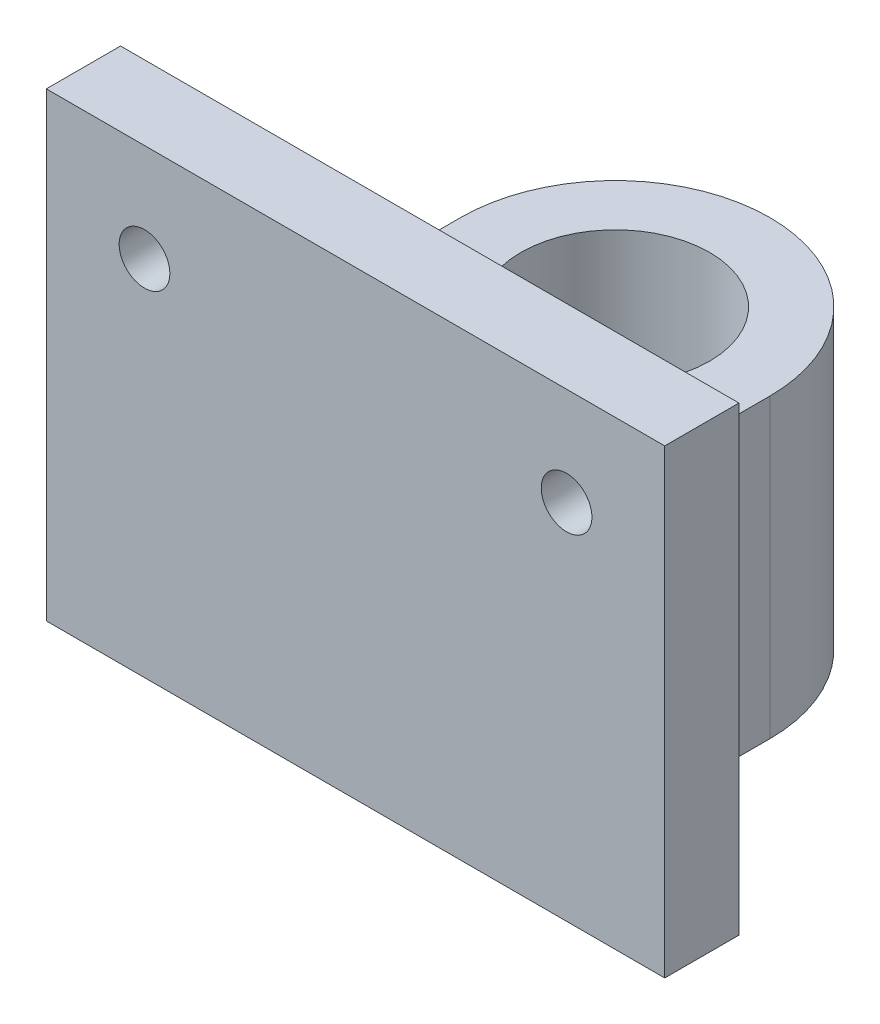
SolidWorks part; units mm, degrees
ref_plane "Front Plane" through (0, 0, 0) normal (0, 0, 1) x (1, 0, 0)
ref_plane "Top Plane" through (0, 0, 0) normal (0, 1, 0) x (1, 0, 0)
ref_plane "Right Plane" through (0, 0, 0) normal (1, 0, 0) x (0, 0, -1)
sketch "Profile-Sketch1" plane through (0, 0, 0) normal (0, 1, 0) x (1, 0, 0)
  line L0 (-25, -21) -> (25, -21)
  line L1 (25, -21) -> (25, -15)
  line L2 (-25, -21) -> (-25, -15)
  line L3 (-25, -15) -> (-22.5, -15)
  line L4 (-12.5, -5) -> (-12.5, 0)
  line L5 (25, -15) -> (22.5, -15)
  line L6 (12.5, -5) -> (12.5, 0)
  circle A0 centre (0, 0) radius 7.625
  arc A6 (12.5, 0) -> (-12.5, 0) centre (0, 0) ccw
  arc A7 (22.5, -15) -> (12.5, -5) centre (22.5, -5) cw
  arc A8 (-12.5, -5) -> (-22.5, -15) centre (-22.5, -5) cw
  dimension "D1" = 15.25
  dimension "D2" = 12.5
  dimension "D7" = 10
  dimension "D3" = 50
  dimension "D4" = 25
  dimension "D5" = 21
  dimension "D6" = 6
extrude "Profile-Boss-Extrude2" add sketch "Profile-Sketch1" along normal blind 37.2599
sketch "FasteningHoleSketch3" plane through (0, 0, 21) normal (0, 0, 1) x (1, 0, 0)
  line L0 (25, 37.2599) -> (25, 0) construction
  line L1 (-25, 37.2599) -> (-25, 0) construction
  line L2 (-25, 0) -> (25, 0) construction
  circle A2 centre (-17.0625, 29.3224) radius 2.05
  circle A3 centre (17.0625, 29.3224) radius 2.05
  dimension "D3" = 4.1
  dimension "D6" = 7.9375
  dimension "D2" = 29.3224
  dimension "D1" = 7.9375
extrude "FasteningHoleCut-Extrude8" cut sketch "FasteningHoleSketch3" against normal through all
sketch "LM8UUPlugSketch1" plane through (0, 0, 0) normal (0, -1, 0) x (1, 0, 0)
  circle A0 centre (0, 0) radius 7.625
  circle A1 centre (0, 0) radius 7.625 construction
  circle A2 centre (0, 0) radius 4.5
  dimension "D1" = 9
extrude "LM8UU plugBoss-Extrude1" add sketch "LM8UUPlugSketch1" along normal blind 0.0001 and the other way blind 1
sketch "Sketch2" plane through (0, 37.2599, 0) normal (0, 1, 0) x (1, 0, 0)
  line L0 (-12.5, 0) -> (-12.5, -5)
  line L1 (12.5, 0) -> (12.5, -5)
  line L2 (-22.5, -15) -> (22.5, -15)
  arc A0 (12.5, 0) -> (-12.5, 0) centre (0, 0) ccw
  arc A1 (12.5, 0) -> (-12.5, 0) centre (0, 0) ccw construction
  arc A2 (-22.5, -15) -> (-12.5, -5) centre (-22.5, -5) ccw
  arc A3 (-22.5, -15) -> (-12.5, -5) centre (-22.5, -5) ccw construction
  arc A4 (12.5, -5) -> (22.5, -15) centre (22.5, -5) ccw
  arc A5 (12.5, -5) -> (22.5, -15) centre (22.5, -5) ccw construction
extrude "Cut-Extrude1" cut sketch "Sketch2" against normal blind 13.2599
equation "\"RailThickness\"= .125in'Spec"
equation "\"LM8UUDiameter\"= 15mm + .25mm'Add  .15mm for printing"
equation "\"MidLeftOrRightSideRailHeight\"= 2.0in"
equation "\"RodStabilizerLength\"= 50mm"
equation "\"HoleOffsetFromEdge\"= \"RailThickness\" * 2.5"
equation "\"StepperMountingHoleOffsetFromItsSide\"= 5.5mm'Spec"
equation "\"StepperMountingHoleOffsetFromLeftOrRightSide\"= \"StepperMountingHoleOffsetFromItsSide\" + \"RailThickness\""
equation "\"StepperMountingHoleDistance\"= 31mm'Spec"
equation "\"LM8UUHeight\"= 24mm'Spec"
equation "\"ZAxisLeadScrewLength\"= 200mm"
equation "\"LegHeight\"= 70mm'Space needed for PSU/Stepper/Electronics"
equation "\"V1 BottomOfLowerRail\"= \"LegHeight\""
equation "\"StepperShaftLength\"= 24mm'Pulley will be attached to the end"
equation "\"V2 ToBedAtTopOfZAxis\"= \"V1 BottomOfLowerRail\" - \"LowerEnclosureThickness\" + \"StepperShaftLength\" + \"ZAxisLeadScrewLength\" - \"LM8UUHeight\" / 2'Equals 277"
equation "\"HotEndToTopOfXAxisGB\"= 71.68487mm'Equals 71.68487. Measured after installed onto X-Axis linear rail guide block"
equation "\"TopOfGBToBottomOfLinearRail\"= \"LinearGBWidth\" / 2 + \"LinearRailWidth\" / 2'Equals 19.5"
equation "\"LinearGBWidth\"= 27mm'Spec"
equation "\"V5 ToBottomOfXAxisLinearRail\"= \"V4 ToTopOfBuildPlate/HotEndTip\" + \"HotEndToTopOfXAxisGB\" - \"TopOfGBToBottomOfLinearRail\"'Equals 352.18487"
equation "\"LinearRailWidth\"= 12mm'Spec"
equation "\"V6 ToMiddleOfYAxisGantryBlock\"= \"V5 ToBottomOfXAxisLinearRail\" - \"GABHeight\" / 2'Equals 334.18487"
equation "\"GABUpperHeight\"= 4mm"
equation "\"GABMidWallHeight\"= 28mm'Must equal 28 or changes alignment"
equation "\"BedToBuildPlateStandoffLength\"= 15mm"
equation "\"BuildPlateHeight\"= 8mm'Spec"
equation "\"V4 ToTopOfBuildPlate/HotEndTip\"= \"V2 ToBedAtTopOfZAxis\" + \"BedToBuildPlateStandoffLength\" + \"BuildPlateHeight\""
equation "\"RodStabilizerHeight\"= \"V8 ToBottomOfMidSideRail\" - \"V2 ToBedAtTopOfZAxis\" + \"HoleOffsetFromEdge\" * 2"
equation "\"LowerEnclosureThickness\"= 5mm"
equation "\"D1@Profile-Sketch1\" = \"LM8UUDiameter\""
equation "\"D3@Profile-Sketch1\" = \"RodStabilizerLength\""
equation "\"D4@Profile-Sketch1\" = \"RodStabilizerLength\" / 2"
equation "\"RodStabilizerWidthFromMidRailToZAxisRodCenter\"= \"StepperMountingHoleOffsetFromLeftOrRightSide\" + \"StepperMountingHoleDistance\" / 2 - \"RailThickness\""
equation "\"StandardWallThickness\"= 3mm"
equation "\"D6@Profile-Sketch1\" = \"StandardWallThickness\" * 2"
equation "\"D1@Profile-Boss-Extrude2\"= \"RodStabilizerHeight\""
equation "\"D6@FasteningHoleSketch3\"=\"HoleOffsetFromEdge\""
equation "\"V8 ToTopOfMidSideRail\"= \"V6 ToMiddleOfYAxisGantryBlock\" + \"MidSideRailVerticalOffset\"'Equals 349.18487"
equation "\"D5@Profile-Sketch1\"=\"RodStabilizerWidthFromMidRailToZAxisRodCenter\""
equation "\"RodStabilizerMountingHoleYOffsetFromBottom\"= \"RodStabilizerHeight\" - \"HoleOffsetFromEdge\""
equation "\"D2@FasteningHoleSketch3\"=\"RodStabilizerMountingHoleYOffsetFromBottom\""
equation "\"D3@FasteningHoleSketch3\"=\"M3HeatInsertHoleDiameter\""
equation "\"GABLowerHeight\"= 4mm"
equation "\"GABHeight\"= \"GABLowerHeight\" + \"GABMidWallHeight\" + \"GABUpperHeight\""
equation "\"V8 ToBottomOfMidSideRail\"= \"V8 ToTopOfMidSideRail\" - \"MidLeftOrRightSideRailHeight\"'Equals 298.38487"
equation "\"MidSideRailVerticalOffset\"= \"LinearRailWidth\" + 3mm'Allows space for RodStabilizer to attach to bottom of MidSideRail"
equation "\"M3HeatInsertHoleDiameter\"= 4mm + .1mm'Add .1mm for printing"
equation "\"D1@Cut-Extrude1\"=\"RodStabilizerHeight\"-\"LM8UUHeight\""
equation "\"LeadScrewHoleDiameter\"= 9mm"
equation "\"D1@LM8UUPlugSketch1\"=\"LeadScrewHoleDiameter\""
